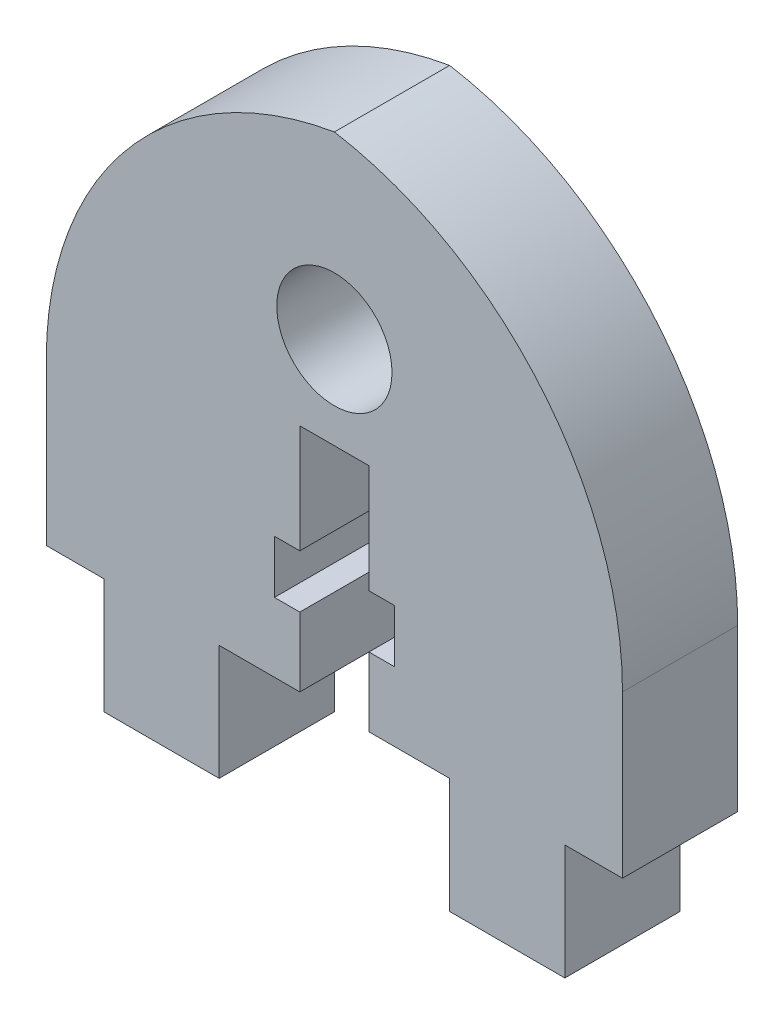
SolidWorks part; units mm, degrees
ref_plane "Front Plane" through (0, 0, 0) normal (0, 0, 1) x (1, 0, 0)
ref_plane "Top Plane" through (0, 0, 0) normal (0, 1, 0) x (1, 0, 0)
ref_plane "Right Plane" through (0, 0, 0) normal (1, 0, 0) x (0, 0, -1)
sketch "Sketch1" plane through (0, 0, 0) normal (0, 0, 1) x (1, 0, 0)
  line L0 (0, 0) -> (0, 13.8708) construction
  line L1 (-12.5, -14) -> (12.5, -14)
  line L2 (-12.5, -14) -> (-12.5, 8)
  line L3 (-12.5, 8) -> (12.5, 8)
  line L4 (12.5, -14) -> (12.5, 8)
  line L5 (0, 0) -> (10.7173, 0) construction
  circle A0 centre (0, 0) radius 2.5
  point P0 (0, 0)
  line B0 (-2.6, -11) -> (-2.6, -8.7)
  line B1 (1.5, -8.7) -> (1.5, -4)
  line B2 (-1.5, -4) -> (-1.5, -8.7)
  line B3 (-2.6, -8.7) -> (-1.5, -8.7)
  line B4 (0, -14) -> (0, -2.7792) construction
  line B5 (-1.5, -14) -> (-5, -14)
  line B6 (-5, -19) -> (-10, -19)
  line B7 (-10, -19) -> (-10, -14)
  line B8 (-5, -19) -> (-5, -14)
  line B9 (1.5, -14) -> (5, -14)
  line B10 (5, -14) -> (5, -19)
  line B11 (5, -19) -> (10, -19)
  line B12 (10, -19) -> (10, -14)
  line B13 (1.5, -4) -> (-1.5, -4)
  line B14 (1.5, -14) -> (1.5, -11)
  line B15 (-1.5, -11) -> (-1.5, -14)
  line B16 (-1.5, -14) -> (1.5, -14) construction
  line B17 (1.5, -8.7) -> (2.6, -8.7)
  line B18 (2.6, -11) -> (1.5, -11)
  line B19 (-1.5, -11) -> (-2.6, -11)
  line B20 (2.6, -8.7) -> (2.6, -11)
  line B21 (0, -4) -> (0, -14) construction
  dimension "D1" = 14
  dimension "D4" = 5
  dimension "D2" = 8
  dimension "D3" = 25
sketch_block_instance "Insert M3 plots ep 5mm-1"
sketch_block "Insert M3 plots ep 5mm" parameters "D1"=10, "D2"=5, "D3"=5
sketch_block_instance "Decoupe Insert M3-4"
sketch_block "Decoupe Insert M3" parameters "D1"=5.2, "D2"=3, "D3"=2.3, "D4"=3, "D5"=10
extrude "Boss-Extrude1" add sketch "Sketch1" along normal blind 5 contours B15 B19 B0 B3 B2 B13 B1 B17 B20 B18 B14 L1 L4 L3 L2 A0 | B6 B8 L1 B7 | B11 B12 L1 B10 region at (0, -2.6855, 0) region at (-7.5, -16.5, 0) region at (7.5, -16.5, 0)
fillet "Fillet1" radius 15 2 edges at (-12.5, 8, 2.5) (12.5, 8, 2.5)
